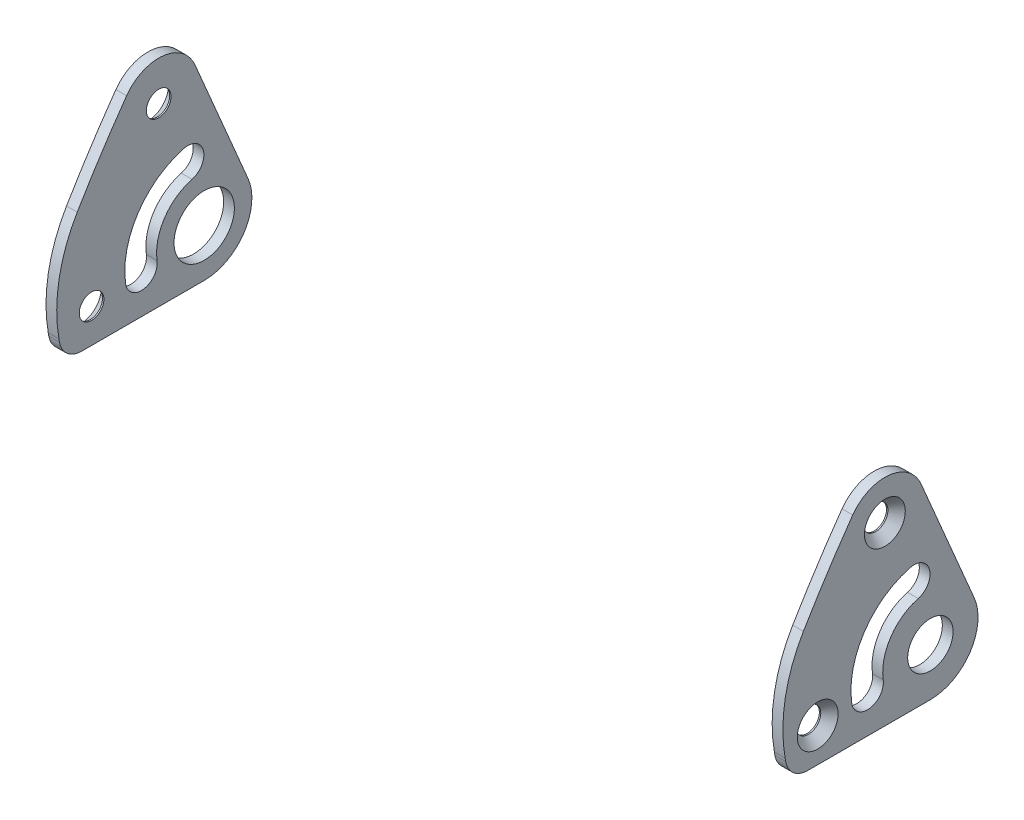
SolidWorks part; units mm, degrees
material "Ti-6Al-4VSolution treated and aged (SS)"
ref_plane "Front Plane" through (0, 0, 0) normal (0, 0, 1) x (1, 0, 0)
ref_plane "Top Plane" through (0, 0, 0) normal (0, 1, 0) x (1, 0, 0)
ref_plane "Right Plane" through (0, 0, 0) normal (1, 0, 0) x (0, 0, -1)
sketch "Sketch1" plane through (50.05, 0, 0) normal (1, 0, 0) x (0, 0, -1)
  line L1 (-163.3043, 20.32) -> (-154.1497, 20.32) construction
  line L2 (-171.4659, 20.32) -> (-151.65, 20.32)
  line L4 (-171.4659, 20.32) -> (-171.9734, 23.4009)
  line L6 (-145.5125, 29.5927) -> (-156.659, 55.852)
  arc A1 (-169.4172, 37.4866) -> (-156.659, 55.852) centre (-38.2131, -40.0455) cw
  circle A2 centre (-151.65, 26.9875) radius 4.2227
  arc A4 (-140.1251, 73.2669) -> (-169.4172, 37.4866) centre (-38.2131, -40.0455) ccw construction
  arc A6 (-171.97, -24.13) -> (-171.9734, 23.4009) centre (-306.6951, -0.3743) ccw construction
  arc A7 (-151.65, 20.32) -> (-145.5125, 29.5927) centre (-151.65, 26.9875) ccw
  arc A9 (-169.4172, 37.4866) -> (-171.9734, 23.4009) centre (-151.65, 26.9875) ccw construction
  arc A10 (-169.4172, 37.4866) -> (-171.9734, 23.4009) centre (-151.65, 26.9875) ccw
  arc A12 (-152.943, 47.0978) -> (-162.5121, 48.1333) centre (-158.0167, 44.9442) ccw
  dimension "D1" = 8.4455
  dimension "D2" = 5.5118
  dimension "D3" = 67
extrude "Boss-Extrude1" add sketch "Sketch1" along normal blind 1.5 contours L6 A12 A1 L2 A7 A2 region at (50.05, 33.3489, 159.6806)
sketch "Sketch2" plane through (51.55, 0, 0) normal (1, 0, 0) x (0, 0, -1)
  line L4 (-161.5796, 23.495) -> (-166.5679, 23.495) construction
  line L6 (-151.6877, 36.0148) -> (-154.2317, 42.0081) construction
  line L9 (-145.5125, 29.5927) -> (-152.943, 47.0978) construction
  line L10 (-171.4659, 20.32) -> (-151.65, 20.32) construction
  arc A9 (-151.65, 20.32) -> (-145.5125, 29.5927) centre (-151.65, 26.9875) ccw construction
  arc A12 (-153.3517, 33.4342) -> (-158.2491, 26.035) centre (-151.65, 26.9875) ccw
  arc A16 (-154.4862, 37.732) -> (-162.6485, 25.4) centre (-151.65, 26.9875) ccw
  arc A18 (-153.3517, 33.4342) -> (-154.4862, 37.732) centre (-153.9189, 35.5831) ccw
  arc A19 (-158.2491, 26.035) -> (-162.6485, 25.4) centre (-160.4488, 25.7175) cw
  dimension "D1" = 3.175
  dimension "D2" = 3.175
  dimension "D3" = 11.1125
extrude "Cut-Extrude1" cut sketch "Sketch2" against normal up to next and the other way through all contours L6 A16 L4 A12 region at (51.55, 31.2975, 158.1618)
fillet "Fillet3" radius 3.175 1 edges at (50.8, 20.32, 171.4659)
hole_wizard "CSK for #4 Flat Head Machine Screw1" positions "Sketch4" profile "Sketch6" countersink size "#4" standard "ANSI Inch" end condition up to next
sketch "Sketch4" plane through (51.55, 0, 0) normal (1, 0, 0) x (0, 0, -1)
  line L0 (-168.7712, 20.32) -> (-151.65, 20.32) construction
  arc A0 (-152.943, 47.0978) -> (-162.5121, 48.1333) centre (-158.0167, 44.9442) ccw construction
  circle A1 centre (-167.4103, 25.0825) radius 4.7625 construction
  arc A4 (-154.4862, 37.732) -> (-162.6485, 25.4) centre (-151.65, 26.9875) ccw construction
  point P0 (-167.4103, 25.0825)
  point P3 (-158.0167, 44.9442)
sketch "Sketch6" plane through (51.55, 25.0825, 167.4103) normal (0, 1, 0) x (0, 0, -1)
  line L0 (0, 0) -> (0, 1.5)
  line L1 (0, 1.5) -> (1.7272, 1.5)
  line L2 (1.7272, 1.5) -> (1.7272, 1.3003)
  line L3 (1.7272, 1.3003) -> (2.8575, 0)
  line L5 (2.8575, 0) -> (0, 0)
  line L6 (-1.7272, 1.3003) -> (-2.8575, 0) construction
  line L11 (0, -6.35) -> (0, 107.95) construction
  dimension "Thru Hole Dia." = 3.4544
  dimension "Thru Hole Depth" = 1.5
  dimension "Near C'Sink Dia." = 5.715
  dimension "Near C'Sink Angle" = 82
mirror "Mirror2" about plane through (0, 0, 0) normal (1, 0, 0) of bodies 110 101
sketch "Sketch7" plane through (51.55, 0, 0) normal (1, 0, 0) x (0, 0, -1)
  circle A0 centre (-151.65, 26.9875) radius 4.2227 construction
  circle A1 centre (-151.65, 26.9875) radius 4.2227
  circle A2 centre (-151.65, 26.9875) radius 3.175
  dimension "D1" = 6.35
extrude "Boss-Extrude2" add sketch "Sketch7" against normal up to surface (1.5 mm away) up to face at (50.05, 25.0825, 165.6831)
equation "\"weapon shaft threads\"= 5 / 16"
equation "\"D1@Sketch1\"=\"weapon shaft threads\" + .02in"
equation "\"D1@Boss-Extrude1\"=1.5mm"
